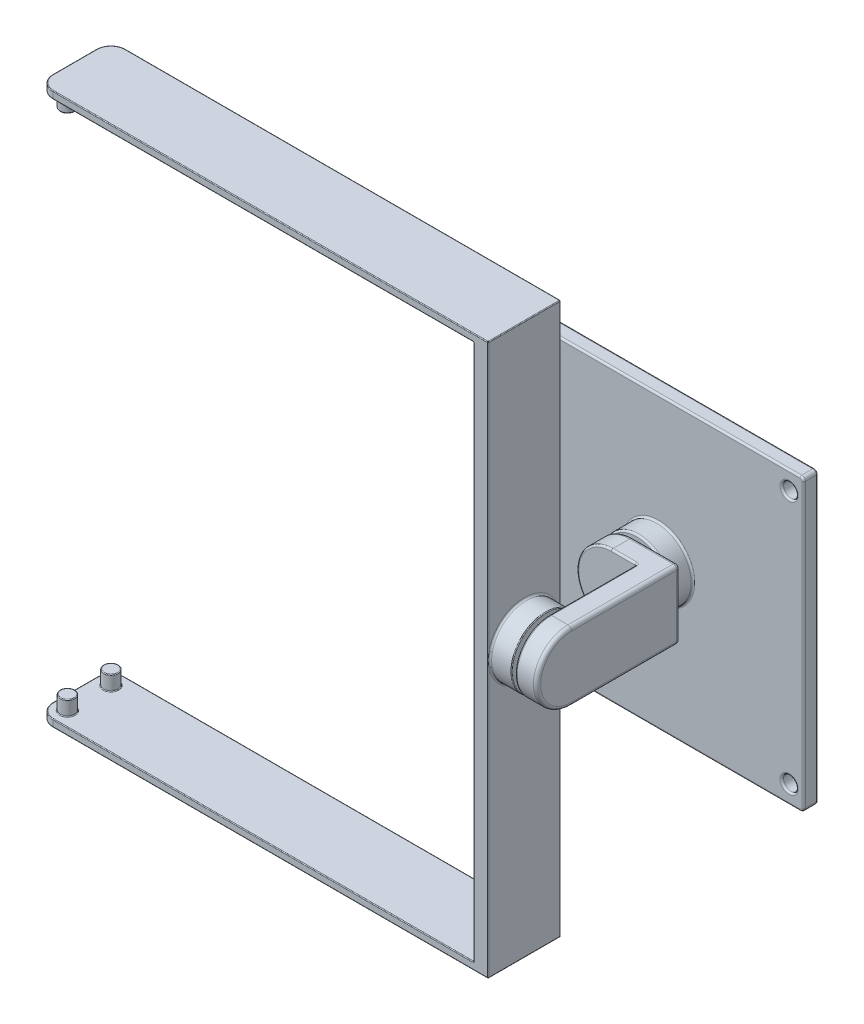
SolidWorks part; units mm, degrees
material "1060 Alloy"
ref_plane "Front Plane" through (0, 0, 0) normal (0, 0, 1) x (1, 0, 0)
ref_plane "Top Plane" through (0, 0, 0) normal (0, 1, 0) x (1, 0, 0)
ref_plane "Right Plane" through (0, 0, 0) normal (1, 0, 0) x (0, 0, -1)
sketch "Sketch1" plane through (0, 0, 0) normal (0, 0, 1) x (1, 0, 0)
  line L0 (0, -37) -> (0, 37)
  line L1 (0, 37) -> (-60, 37)
  line L2 (-60, 37) -> (-60, 38)
  line L3 (-60, 38) -> (2, 38)
  line L4 (2, 38) -> (2, -38)
  line L5 (2, -38) -> (-60, -38)
  line L6 (-60, -38) -> (-60, -37)
  line L7 (-60, -37) -> (0, -37)
  point P4 (0, 0)
  dimension "D1" = 74
  dimension "D2" = 1
  dimension "D3" = 2
  dimension "D4" = 60
extrude "Boss-Extrude1" add sketch "Sketch1" along normal blind 10
sketch "Sketch2" plane through (0, 0, 0) normal (0, 1, 0) x (1, 0, 0)
  line L0 (2, -5) -> (-60, -5) construction
  line L1 (2, -10) -> (2, 0) construction
  line L2 (-60, -10) -> (-60, 0) construction
  circle A0 centre (-58, -2) radius 1
  circle A1 centre (-58, -8) radius 1
  dimension "D1" = 2
  dimension "D2" = 2
  dimension "D3" = 6
extrude "Boss-Extrude2" add sketch "Sketch2" along normal blind 2 from surface starting at face at (-30, -37, 5)
extrude "Boss-Extrude3" add sketch "Sketch2<2>" against normal blind 2 from surface starting at face at (-30, 37, 5)
sketch "Sketch2<2>" plane through (0, 0, 0) normal (0, 1, 0) x (1, 0, 0) same geometry as "Sketch2"
fillet "Fillet1" radius 2 4 edges at (-60, -37.5, 10) (-60, 37.5, 10) (-60, 37.5, 0) (-60, -37.5, 0)
fillet "Fillet2" radius 0.1 36 edges at (0, 0, 0) (0, 0, 10) (0, 37, 5) (-29, 37, 0) (-59.4142, 37, 0.5858) (-60, 37, 5) (-59.4142, 37, 9.4142) (-29, 37, 10) (-59, 37, 2) (-59, 37, 8) (-59.4142, -37, 0.5858) (-29, -37, 0) (0, -37, 5) (-29, -37, 10) (-59.4142, -37, 9.4142) (-60, -37, 5) (-58, -37, 1) (-58, -37, 7) (2, 0, 10) (2, 0, 0) (2, -38, 5) (-28, -38, 0) (-59.4142, -38, 0.5858) (-60, -38, 5) (-59.4142, -38, 9.4142) (-28, -38, 10) (-59.4142, 38, 0.5858) (-28, 38, 0) (2, 38, 5) (-28, 38, 10) (-59.4142, 38, 9.4142) (-60, 38, 5) (-59, 35, 2) (-59, 35, 8) (-58, -35, 1) (-58, -35, 7)
sketch "Sketch4" plane through (2, 0, 0) normal (1, 0, 0) x (0, 0, -1)
  line L0 (-5, 37.9) -> (-5, -37.9) construction
  line L1 (-0.1, 37.9) -> (-9.9, 37.9) construction
  line L2 (-9.9, -37.9) -> (-0.1, -37.9) construction
  circle A0 centre (-5, 0) radius 4.75
  dimension "D1" = 9.5
extrude "Boss-Extrude4" add sketch "Sketch4" along normal blind 3
fillet "Fillet3" radius 0.1 1 edges at (5, 4.75, 5)
sketch "Sketch5" plane through (5, 0, 0) normal (1, 0, 0) x (0, 0, -1)
  circle A0 centre (-5, 0) radius 3
  dimension "D1" = 6
extrude "Boss-Extrude5" add sketch "Sketch5" along normal blind 0.5
sketch "Sketch6" plane through (5.5, 0, 0) normal (1, 0, 0) x (0, 0, -1)
  circle A0 centre (-5, 0) radius 4.75 construction
  circle A1 centre (-5, 0) radius 4.75
extrude "Boss-Extrude6" add sketch "Sketch6" along normal blind 3
sketch "Sketch7" plane through (8.5, 0, 0) normal (1, 0, 0) x (0, 0, -1)
  line L1 (-5, 4.75) -> (10, 4.75)
  line L2 (-5, 4.75) -> (-5, -4.75)
  line L3 (-5, -4.75) -> (10, -4.75)
  line L4 (10, 4.75) -> (10, -4.75)
  circle A0 centre (-5, 0) radius 4.75 construction
  circle A1 centre (-5, 0) radius 4.75 construction
  dimension "D1" = 15
  dimension "D2" = 9.5
extrude "Boss-Extrude7" add sketch "Sketch7" against normal up to surface (3 mm away) up to face at (5.5, 3, 5)
sketch "Sketch9" plane through (0, 0, -10) normal (0, 0, -1) x (-1, 0, 0)
  line L1 (-2, 4.75) -> (-2, -4.75) construction
  line L2 (-8.5, 4.75) -> (-2, 4.75)
  line L3 (-8.5, 4.75) -> (-8.5, -4.75)
  line L4 (-8.5, -4.75) -> (-2, -4.75)
  arc A0 (-2, -4.75) -> (-2, 4.75) centre (-2, 0) ccw
  dimension "D1" = 9.5
extrude "Boss-Extrude8" add sketch "Sketch9" against normal blind 3
sketch "Sketch10" plane through (0, 0, -10) normal (0, 0, -1) x (-1, 0, 0)
  circle A0 centre (-2, 0) radius 3
  dimension "D1" = 6
extrude "Boss-Extrude9" add sketch "Sketch10" along normal blind 0.5
sketch "Sketch11" plane through (0, 0, -10.5) normal (0, 0, -1) x (-1, 0, 0)
  circle A0 centre (-2, 0) radius 4.75
  arc A1 (-2, -4.75) -> (-2, 4.75) centre (-2, 0) ccw construction
extrude "Boss-Extrude10" add sketch "Sketch11" along normal blind 3
sketch "Sketch12" plane through (0, 0, -13.5) normal (0, 0, -1) x (-1, 0, 0)
  line L1 (-22, 20) -> (18, 20)
  line L2 (-22, 20) -> (-22, -20)
  line L3 (-22, -20) -> (18, -20)
  line L4 (18, 20) -> (18, -20)
  line L5 (-2, -20) -> (-2, 20) construction
  line L6 (-22, 0) -> (18, 0) construction
  point P0 (-2, 0)
  dimension "D1" = 40
  dimension "D2" = 40
extrude "Boss-Extrude11" add sketch "Sketch12" along normal blind 2
fillet "Fillet4" radius 0.5 4 edges at (22, -20, -14.5) (-18, -20, -14.5) (22, 20, -14.5) (-18, 20, -14.5)
sketch "Sketch13" plane through (0, 0, -15.5) normal (0, 0, -1) x (-1, 0, 0)
  line L0 (-2, 20) -> (-2, -20) construction
  line L1 (17.5, 20) -> (-21.5, 20) construction
  line L2 (-21.5, -20) -> (17.5, -20) construction
  line L3 (-22, 0) -> (18, 0) construction
  line L4 (-22, 19.5) -> (-22, -19.5) construction
  line L5 (18, -19.5) -> (18, 19.5) construction
  circle A0 centre (16, 17.5) radius 1
  circle A1 centre (-20, 17.5) radius 1
  circle A2 centre (-20, -17.5) radius 1
  circle A3 centre (16, -17.5) radius 1
  dimension "D1" = 2
  dimension "D2" = 18
  dimension "D3" = 2.5
extrude "Cut-Extrude1" cut sketch "Sketch13" against normal up to next
fillet "Fillet5" radius 0.5 7 edges at (5.25, -4.75, -10) (-2.75, 0, -10) (8.5, 4.75, -2.5) (8.5, -4.75, -2.5) (8.5, 0, -10) (5.25, 4.75, -10) (8.5, 0, 9.75)
fillet "Fillet6" radius 0.25 34 edges at (5.5, 4.75, -1) (5.5, -4.75, -1) (21.8536, 19.8536, -15.5) (2, 20, -15.5) (-17.8536, 19.8536, -15.5) (-18, 0, -15.5) (-17.8536, -19.8536, -15.5) (2, -20, -15.5) (21.8536, -19.8536, -15.5) (22, 0, -15.5) (-17, 17.5, -15.5) (19, -17.5, -15.5) (21, 17.5, -15.5) (-15, -17.5, -15.5) (-17.8536, -19.8536, -13.5) (-18, 0, -13.5) (-17.8536, 19.8536, -13.5) (2, 20, -13.5) (21.8536, 19.8536, -13.5) (22, 0, -13.5) (21.8536, -19.8536, -13.5) (2, -20, -13.5) (-17, 17.5, -13.5) (19, -17.5, -13.5) (19, 17.5, -13.5) (-17, -17.5, -13.5) (-2.75, 0, -10.5) (-2.75, 0, -13.5) (-2.75, 0, -7) (3.75, 4.75, -7) (5.5, 0, -7) (3.75, -4.75, -7) (2, -4.75, 5) (5.5, 0, 9.75)
